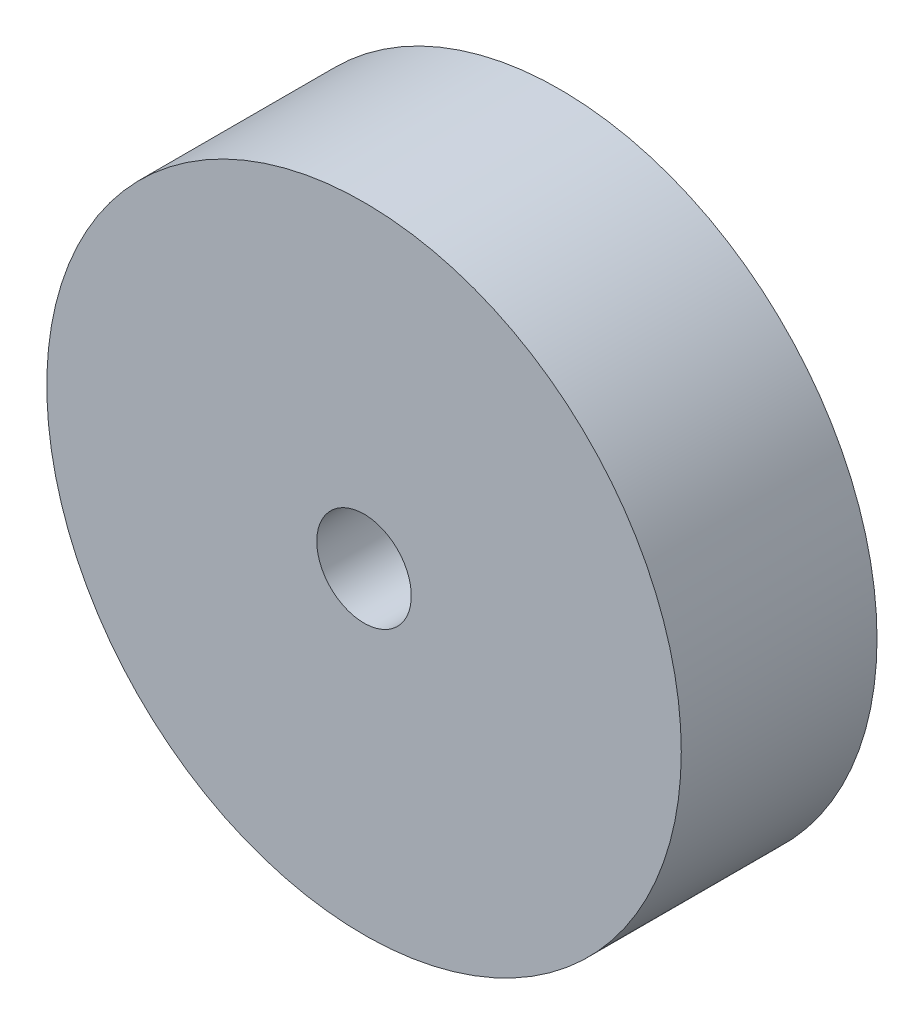
SolidWorks part; units mm, degrees
ref_plane "Front Plane" through (0, 0, 0) normal (0, 0, 1) x (1, 0, 0)
ref_plane "Top Plane" through (0, 0, 0) normal (0, 1, 0) x (1, 0, 0)
ref_plane "Right Plane" through (0, 0, 0) normal (1, 0, 0) x (0, 0, -1)
sketch "Sketch1" plane through (0, 0, 0) normal (0, 0, 1) x (1, 0, 0)
  circle A0 centre (-29.0823, -1.7038) radius 9.4
  dimension "D1" = 18.8
extrude "Boss-Extrude1" add sketch "Sketch1" along normal blind 5.8
sketch "Sketch2" plane through (0, 0, 0) normal (0, 0, -1) x (-1, 0, 0)
  circle A0 centre (29.0823, -1.7038) radius 7.9
  dimension "D1" = 15.8
extrude "Cut-Extrude1" cut sketch "Sketch2" against normal blind 3.2
sketch "Sketch3" plane through (0, 0, 3.2) normal (0, 0, -1) x (-1, 0, 0)
  circle A0 centre (29.0823, -1.7038) radius 1
  dimension "D1" = 2
extrude "Boss-Extrude2" add sketch "Sketch3" along normal blind 1.5875
sketch "Sketch4" plane through (0, 0, 1.6125) normal (0, 0, -1) x (-1, 0, 0)
  circle A0 centre (29.0823, -1.7038) radius 3.7
  dimension "D1" = 7.4
extrude "Boss-Extrude3" add sketch "Sketch4" against normal blind 3
sketch "Sketch5" plane through (0, 0, 1.6125) normal (0, 0, -1) x (-1, 0, 0)
  circle A0 centre (29.0823, -1.7038) radius 1.4
  dimension "D1" = 2.8
extrude "Cut-Extrude2" cut sketch "Sketch5" against normal through all
chamfer "Chamfer2" distance 1.7 angle 41 1 edges at (-32.7823, -1.7038, 1.6125) first distance on face at (-32.7823, -1.7038, 3.2)
